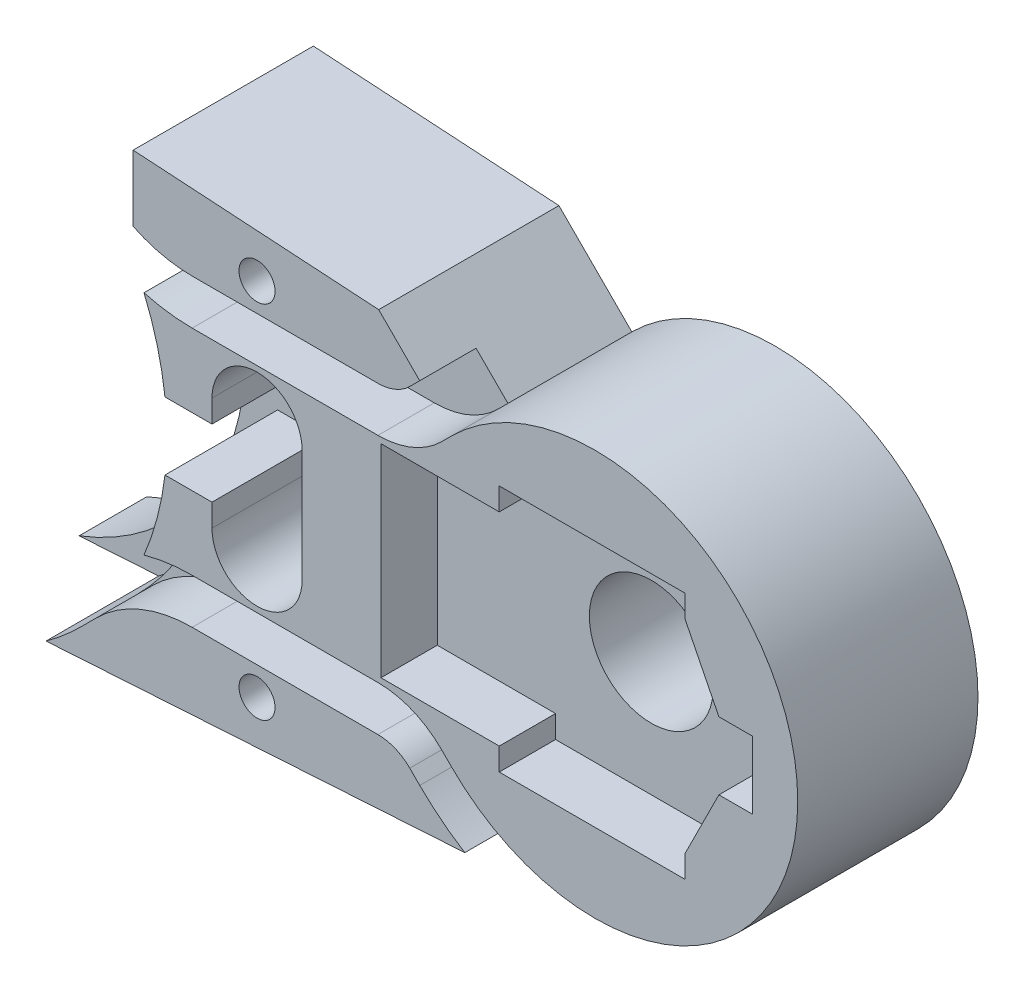
SolidWorks part; units mm, degrees
ref_plane "Front" through (0, 0, 0) normal (0, 0, 1) x (1, 0, 0)
ref_plane "Top" through (0, 0, 0) normal (0, 1, 0) x (1, 0, 0)
ref_plane "Right" through (0, 0, 0) normal (1, 0, 0) x (0, 0, -1)
sketch "Sketch1" plane through (0, 0, 0) normal (0, 0, 1) x (1, 0, 0)
  line L0 (0, 0) -> (32, 0) construction
  line L1 (0, 11) -> (32, 9)
  line L2 (11.5, 0) -> (11.5, 10.2812)
  line L3 (32, -9) -> (0, -11)
  line L4 (32, 0) -> (22.4, 9.6)
  circle A0 centre (0, 0) radius 11.5
  circle A1 centre (32, 0) radius 9
  circle A2 centre (32, 0) radius 2.75
extrude "Boss-Extrude1" add sketch "Sketch1" along normal blind 8 contours A0 L0 A1 L1 | L0 L3 A1 | A1 L0 A2 | L0 A1 A2 region at (17.6428, 5.0157, 0) region at (17.2137, -5.6642, 0) region at (26.2118, 2.3976, 0) region at (26.125, -0.2546, 0)
sketch "Sketch2" plane through (28.2876, 0, 0) normal (0, 0, 1) x (1, 0, 0)
  line L26 (3.7124, 0) -> (10.7124, 0) construction
  line L27 (3.7124, 0) -> (-5.7876, 0) construction
  line L28 (3.7124, 0) -> (3.7124, -5.5) construction
  line L29 (3.7124, 0) -> (3.7124, 5.5) construction
  line L30 (10.7124, 0) -> (10.7124, 1.5)
  line L31 (10.7124, 1.5) -> (9.2124, 1.5)
  line L32 (9.2124, 1.5) -> (7.7124, 1.5) construction
  line L33 (7.7124, 1.5) -> (7.7124, 4.5) construction
  line L34 (9.2124, 1.5) -> (7.7124, 4.5)
  line L35 (7.7124, 4.5) -> (7.7124, 5.5)
  line L36 (7.7124, 5.5) -> (3.7124, 5.5)
  line L37 (3.7124, 5.5) -> (-0.5376, 5.5)
  line L38 (-0.5376, 5.5) -> (-0.5376, 4.5)
  line L39 (-0.5376, 4.5) -> (-5.7876, 4.5)
  line L40 (-5.7876, 4.5) -> (-5.7876, 0)
  line L41 (10.7124, 0) -> (10.7124, -1.5)
  line L42 (10.7124, -1.5) -> (9.2124, -1.5)
  line L43 (9.2124, -1.5) -> (7.7124, -1.5) construction
  line L44 (7.7124, -1.5) -> (7.7124, -4.5) construction
  line L45 (9.2124, -1.5) -> (7.7124, -4.5)
  line L46 (7.7124, -4.5) -> (7.7124, -5.5)
  line L47 (7.7124, -5.5) -> (3.7124, -5.5)
  line L48 (3.7124, -5.5) -> (-0.5376, -5.5)
  line L49 (-0.5376, -5.5) -> (-0.5376, -4.5)
  line L50 (-0.5376, -4.5) -> (-5.7876, -4.5)
  line L51 (-5.7876, -4.5) -> (-5.7876, 0)
extrude "Pot Insert" cut sketch "Sketch2" against normal blind 2.5 from offset 8
sketch "Sketch7" plane through (0, 0, 0) normal (0, 0, 1) x (1, 0, 0)
  line L0 (19, 2.5) -> (19, -2.5)
  line L1 (32, 0) -> (17, 0) construction
  line L2 (15, 2.5) -> (15, 1.5)
  line L3 (17, 0) -> (17, 2.5) construction
  line L4 (15, 1.5) -> (12.9132, 1.5)
  line L5 (17, 0) -> (17, -2.5) construction
  line L6 (15, -2.5) -> (15, -1.5)
  line L7 (15, -1.5) -> (12.9132, -1.5)
  circle A0 centre (0, 0) radius 11
  circle A1 centre (0, 0) radius 13
  circle A3 centre (17, -2.5) radius 2
  circle A4 centre (17, 2.5) radius 2
extrude "Middle Flex/Ext Canal" cut sketch "Sketch7" along normal blind 5 from offset 3 contours A1 A0 | A4 A1 A3 | A4 | A3 | A3 | A3 | A3 | A4 | A4 | A4 region at (17, 2.5, 0) region at (15.6429, 0, 0) region at (17, -2.5, 0) region at (12.6112, 0.73, 0)
sketch "Sketch6" plane through (0, 0, 0) normal (0, 0, 1) x (1, 0, 0)
  line L4 (0, 0) -> (32, 0) construction
  line L7 (0, 0) -> (7.7782, 7.7782) construction
  line L27 (7.7782, -7.7782) -> (9.1924, -9.1924) construction
  line L33 (0, 0) -> (7.7782, -7.7782) construction
  line L34 (17, -6.75) -> (17, -4.75) construction
  line L35 (17, 6.75) -> (17, 4.75) construction
  line L36 (25.636, -6.364) -> (24.2218, -7.7782) construction
  line L37 (32, 0) -> (25.636, -6.364) construction
  line L38 (32, 0) -> (25.636, 6.364) construction
  line L39 (17, -8) -> (17, -6.75) construction
  line L40 (17, 8) -> (17, 6.75) construction
  line L41 (14.1201, 4.75) -> (17, 4.75)
  line L42 (7.7782, 7.7782) -> (8.4632, 7.0931)
  line L43 (9.8774, 8.5074) -> (9.1924, 9.1924)
  line L44 (17, 6.75) -> (14.1201, 6.75)
  line L45 (7.6334, -10.5229) -> (0, -11)
  line L46 (7.7782, -7.7782) -> (8.4632, -7.0931)
  line L47 (14.1201, -6.75) -> (17, -6.75)
  line L48 (9.1924, -9.1924) -> (9.8774, -8.5074)
  line L49 (25.636, 6.364) -> (24.2218, 7.7782)
  line L50 (32, -9) -> (26.2233, -9.361)
  line L51 (22.3652, -4.75) -> (17, -4.75)
  line L52 (25.636, -6.364) -> (25.1937, -5.9216)
  line L53 (22.3652, -6.75) -> (17, -6.75)
  line L54 (17, -4.75) -> (14.1201, -4.75)
  line L55 (24.2218, -7.7782) -> (23.7794, -7.3358)
  line L56 (22.3652, 4.75) -> (17, 4.75)
  line L57 (25.636, 6.364) -> (25.1937, 5.9216)
  line L58 (22.3652, 6.75) -> (17, 6.75)
  line L59 (24.2218, 7.7782) -> (23.7794, 7.3358)
  line L60 (7.7782, 7.7782) -> (9.1924, 9.1924)
  arc A12 (14.1201, -6.75) -> (9.8774, -8.5074) centre (14.1201, -12.75) ccw
  arc A13 (9.8774, 8.5074) -> (14.1201, 6.75) centre (14.1201, 12.75) ccw
  arc A14 (8.4632, -7.0931) -> (14.1201, -4.75) centre (14.1201, -12.75) cw
  arc A15 (8.4632, 7.0931) -> (14.1201, 4.75) centre (14.1201, 12.75) ccw
  arc A16 (7.7782, -7.7782) -> (0, -11) centre (0, 0) cw
  arc A17 (9.1924, -9.1924) -> (7.6334, -10.5229) centre (0, 0) cw
  arc A18 (24.2218, -7.7782) -> (26.2233, -9.361) centre (32, 0) ccw
  arc A19 (25.636, -6.364) -> (32, -9) centre (32, 0) ccw
  arc A20 (22.3652, 6.75) -> (23.7794, 7.3358) centre (22.3652, 8.75) ccw
  arc A21 (22.3652, -6.75) -> (23.7794, -7.3358) centre (22.3652, -8.75) cw
  arc A22 (22.3652, -4.75) -> (25.1937, -5.9216) centre (22.3652, -8.75) cw
  arc A23 (22.3652, 4.75) -> (25.1937, 5.9216) centre (22.3652, 8.75) ccw
extrude "Distal Flex/Ext Canal" cut sketch "Sketch6" along normal blind 2.5 from offset 5.5 contours L56 A23 L57 L49 L59 A20 L58 L44 A13 L43 L60 L42 A15 L41 | A22 L51 L54 A14 L46 A16 L45 A17 L48 A12 L47 L53 A21 L55 A18 L50 A19 L52 region at (16.5616, 6.1499, 0) region at (4.482, -10.4068, 0)
sketch "Sketch3" plane through (0, 0, 0) normal (0, 0, 1) x (1, 0, 0)
  line L0 (32, 0) -> (17, 0) construction
  line L1 (17, 0) -> (17, 8) construction
  line L2 (17, 0) -> (17, -8) construction
  line L3 (17, 0) -> (17, 2.5) construction
  line L4 (17, 0) -> (17, -2.5) construction
  circle A0 centre (17, 8) radius 0.8
  circle A1 centre (17, -8) radius 0.8
  circle A2 centre (17, 2.5) radius 0.8
  circle A3 centre (17, -2.5) radius 0.8
extrude "Screw Holes" cut sketch "Sketch3" along normal through all
